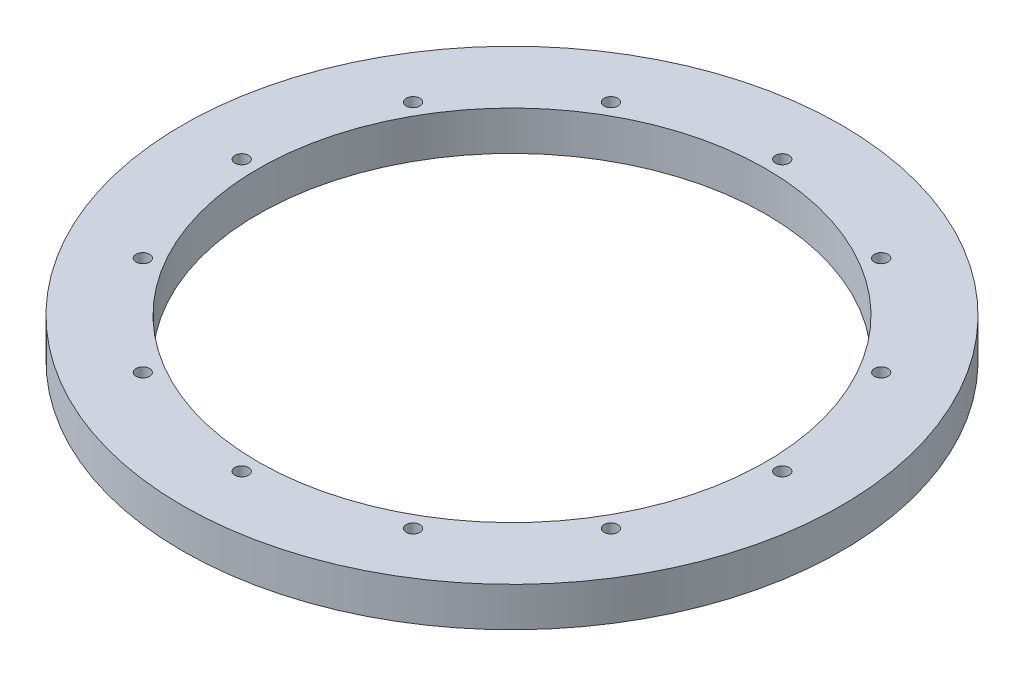
SolidWorks part; units mm, degrees
material "6061 Alloy"
ref_plane "Front Plane" through (0, 0, 0) normal (0, 0, 1) x (1, 0, 0)
ref_plane "Top Plane" through (0, 0, 0) normal (0, 1, 0) x (1, 0, 0)
ref_plane "Right Plane" through (0, 0, 0) normal (1, 0, 0) x (0, 0, -1)
sketch "Sketch1" plane through (0, 0, 0) normal (0, 1, 0) x (1, 0, 0)
  circle A0 centre (0, 0) radius 49.2125
  circle A1 centre (0, 0) radius 63.881
  circle A3 centre (0, -52.3875) radius 1.3208
  circle A4 centre (-26.1938, -45.3689) radius 1.3208
  circle A5 centre (-45.3689, -26.1937) radius 1.3208
  circle A6 centre (-52.3875, 0) radius 1.3208
  circle A7 centre (-45.3689, 26.1938) radius 1.3208
  circle A8 centre (-26.1937, 45.3689) radius 1.3208
  circle A9 centre (0, 52.3875) radius 1.3208
  circle A10 centre (26.1938, 45.3689) radius 1.3208
  circle A11 centre (45.3689, 26.1937) radius 1.3208
  circle A12 centre (52.3875, 0) radius 1.3208
  circle A13 centre (45.3689, -26.1938) radius 1.3208
  circle A14 centre (26.1937, -45.3689) radius 1.3208
  point P21 (0, 0)
  dimension "D1" = 98.425
  dimension "D4" = 2.6416
  dimension "D5" = 52.3875
  dimension "D2" = 14.6685
  dimension "D6" = 12
extrude "Boss-Extrude1" add sketch "Sketch1" along normal blind 7.62 contours A0 | A1 region at (-62.0742, 0, 0)
equation "\"Middle Coupler Inner Daimeter\"= 3.875in"
equation "\"Middle Coupler  Wall Thickness\"= 0.25in"
equation "\"Middle Coupler Bottom Thickness\"= 0.2in"
equation "\"Bearing Rail Offset\"= 0.45in"
equation "\"3-56 UNF Tap\"= 0.089in"
equation "\"3-56 UNF Clearance\"= 0.104in"
equation "\"D5@Sketch1\"=(\"Middle Coupler Inner Daimeter\"*2+0.5)/4in"
equation "\"Ball Bearing Distance\"= 0.03in"
equation "\"D4@Sketch1\"=\"3-56 UNF Clearance\""
equation "\"D1@Sketch1\"=\"Middle Coupler Inner Daimeter\""
equation "\"TCA Outer Diameter\"= 6in"
equation "\"Interstage Aeroframe Wall Thickness\"= 0.072in"
equation "\"Compression Spring OD\"= 0.42in"
equation "\"10-24 Tap\"= 0.157in"
equation "\"10-24 Clearance\"= 0.196in"
equation "\"Lower Stage Fuselage Wall Thickness\"= 0.25in"
equation "\"6-32 Tap\"= 0.107in"
equation "\"1/4-20 Tap\"= 0.201in"
equation "\"D2@Sketch1\"=0.5875 - 10/1000"
